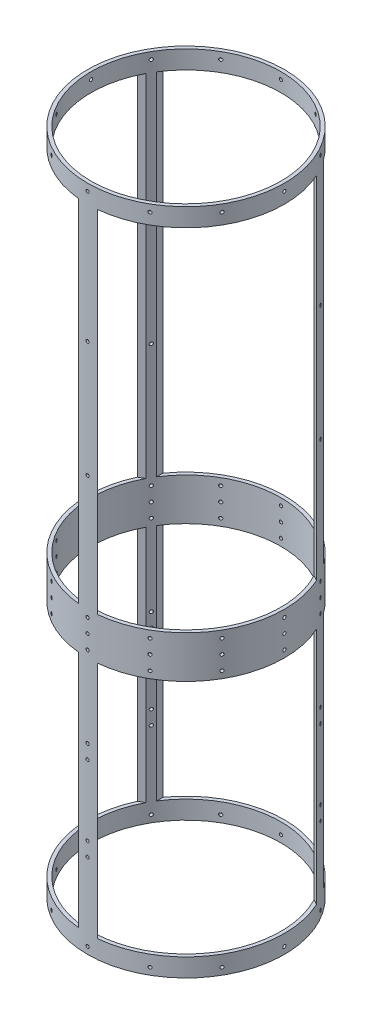
SolidWorks part; units mm, degrees
material "6061-T6 (SS)"
ref_plane "Front Plane" through (0, 0, 0) normal (0, 0, 1) x (1, 0, 0)
ref_plane "Top Plane" through (0, 0, 0) normal (0, 1, 0) x (1, 0, 0)
ref_plane "Right Plane" through (0, 0, 0) normal (1, 0, 0) x (0, 0, -1)
sketch "Sketch1" plane through (0, 0, 0) normal (0, 1, 0) x (1, 0, 0)
  circle A0 centre (0, 0) radius 88.9
  circle A1 centre (0, 0) radius 85.725
  dimension "D1" = 177.8
  dimension "D2" = 171.45
extrude "Boss-Extrude1" add sketch "Sketch1" along normal mid plane 603.25
sketch "Sketch2" plane through (0, 0, 0) normal (0, 0, 1) x (1, 0, 0)
  line L0 (88.9, -301.625) -> (88.9, 301.625) construction
  line L5 (-88.9, -301.625) -> (88.9, -301.625) construction
  line L6 (72.39, -285.115) -> (-72.39, -285.115)
  line L7 (-88.9, 301.625) -> (-88.9, -301.625) construction
  line L9 (72.39, -285.115) -> (72.39, -69.723)
  line L10 (72.39, -69.723) -> (-72.39, -69.723)
  line L11 (-72.39, -285.115) -> (-72.39, -69.723)
  line L12 (85.725, 301.625) -> (-85.725, 301.625) construction
  line L13 (72.39, -31.623) -> (-72.39, -31.623)
  line L14 (72.39, -31.623) -> (72.39, 285.115)
  line L15 (72.39, 285.115) -> (-72.39, 285.115)
  line L16 (-72.39, -31.623) -> (-72.39, 285.115)
  dimension "D1" = 16.51
  dimension "D2" = 16.51
  dimension "D3" = 16.51
  dimension "D4" = 231.902
  dimension "D5" = 16.51
  dimension "D6" = 38.1
extrude "Cut-Extrude1" cut sketch "Sketch2" against normal up to surface (51.6033 mm away) up to face at (0, 301.625, 88.9)
pattern_circular "CirPattern1" count 3 over 360 about axis through (0, 301.625, 0) along (0, -1, 0) of "Cut-Extrude1"
ref_plane "Plane1" through (0, 0, 88.9) normal (0, 0, 1) x (1, 0, 0)
sketch "Sketch3" plane through (0, 0, 88.9) normal (0, 0, 1) x (1, 0, 0)
  line L0 (0, -97.79) -> (0, 97.79) construction
  line L1 (88.9, 301.625) -> (-88.9, 301.625) construction
  circle A0 centre (0, 295.275) radius 1.4351
  dimension "D1" = 2.8702
  dimension "D2" = 6.35
extrude "Cut-Extrude2" cut sketch "Sketch3" against normal blind 25.908
pattern_circular "CirPattern2" count 12 over 360 about axis through (0, 301.625, 0) along (0, -1, 0) of "Cut-Extrude2"
mirror "Mirror1" about plane through (0, 0, 0) normal (0, 1, 0) of "CirPattern2"
sketch "Sketch4" plane through (0, 0, 88.9) normal (0, 0, 1) x (1, 0, 0)
  line L0 (0, -97.79) -> (0, 97.79) construction
  circle A0 centre (0, -225.425) radius 1.4351
  circle A1 centre (0, -212.725) radius 1.4351
  circle A2 centre (0, -295.275) radius 1.4351 construction
  circle A3 centre (0, -149.225) radius 1.4351
  circle A4 centre (0, -136.525) radius 1.4351
  dimension "D1" = 69.85
  dimension "D2" = 2.8702
  dimension "D3" = 12.7
  dimension "D4" = 2.8702
  dimension "D5" = 63.5
  dimension "D6" = 12.7
  dimension "D7" = 2.8702
  dimension "D8" = 2.8702
extrude "Cut-Extrude3" cut sketch "Sketch4" against normal blind 34.798
pattern_circular "CirPattern3" count 3 over 360 about axis through (0, 301.625, 0) along (0, -1, 0) of "Cut-Extrude3" reverse direction yes
sketch "Sketch5" plane through (0, 0, 88.9) normal (0, 0, 1) x (1, 0, 0)
  line L0 (0, -97.79) -> (0, 97.79) construction
  line L1 (-8.4947, -31.623) -> (-88.9, -31.623) construction
  line L2 (-88.9, -69.723) -> (-8.4947, -69.723) construction
  line L3 (88.9, -31.623) -> (8.4947, -31.623) construction
  circle A0 centre (0, -50.673) radius 1.4351
  circle A1 centre (0, 73.025) radius 1.4351
  circle A2 centre (0, 177.927) radius 1.4351
  circle A3 centre (0, 295.275) radius 1.4351 construction
  circle A4 centre (0, -37.973) radius 1.4351
  circle A5 centre (0, -63.373) radius 1.4351
  dimension "D1" = 2.8702
  dimension "D3" = 117.348
  dimension "D5" = 2.8702
  dimension "D6" = 2.8702
  dimension "D4" = 123.698
  dimension "D7" = 2.8702
  dimension "D8" = 2.8702
  dimension "D9" = 6.35
  dimension "D10" = 6.35
  dimension "D2" = 19.05
extrude "Cut-Extrude4" cut sketch "Sketch5" against normal blind 87.63
pattern_circular "CirPattern4" count 12 over 360 about axis through (0, 301.625, 0) along (0, -1, 0) of "Cut-Extrude4" reverse direction yes
